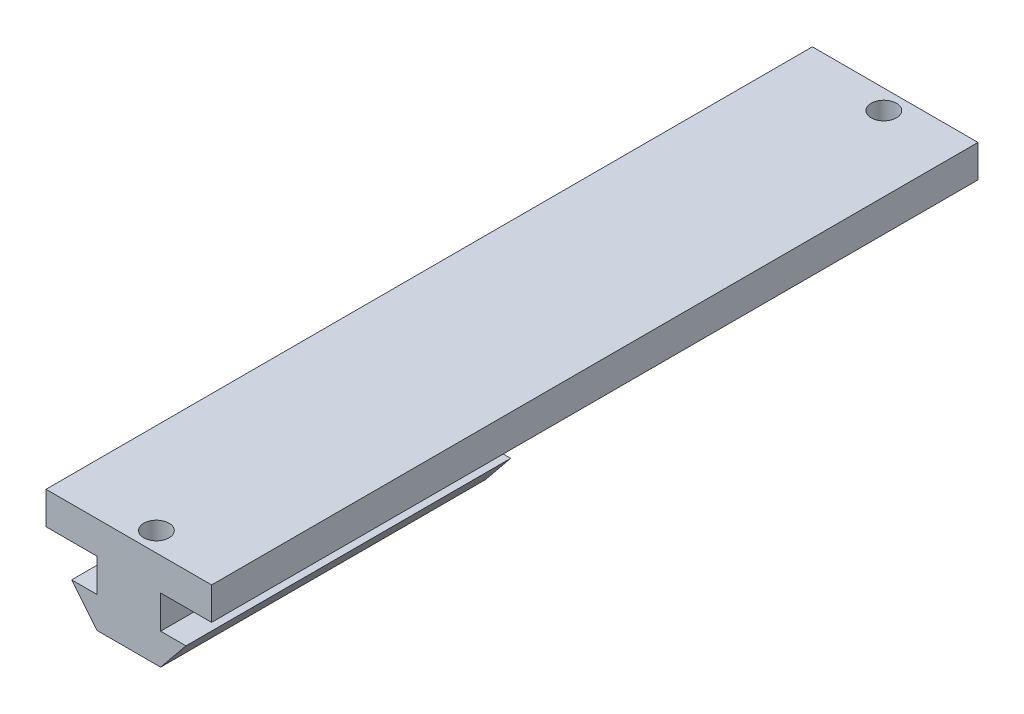
SolidWorks part; units mm, degrees
ref_plane "Front Plane" through (0, 0, 0) normal (0, 0, 1) x (1, 0, 0)
ref_plane "Top Plane" through (0, 0, 0) normal (0, 1, 0) x (1, 0, 0)
ref_plane "Right Plane" through (0, 0, 0) normal (1, 0, 0) x (0, 0, -1)
sketch "Sketch1" plane through (0, 0, 0) normal (0, 1, 0) x (1, 0, 0)
  line L1 (-12.75, -59) -> (12.75, -59)
  line L2 (-12.75, -59) -> (-12.75, 59)
  line L3 (-12.75, 59) -> (12.75, 59)
  line L4 (12.75, -59) -> (12.75, 59)
  line L5 (-12.75, -59) -> (12.75, 59) construction
  line L6 (-12.75, 59) -> (12.75, -59) construction
  point P0 (0, 0)
  dimension "D1" = 118
  dimension "D2" = 25.5
extrude "Boss-Extrude1" add sketch "Sketch1" along normal blind 5
sketch "Sketch2" plane through (0, 5, 0) normal (0, 1, 0) x (1, 0, 0)
  line L0 (12.75, 0) -> (-12.75, 0) construction
  line L1 (12.75, -59) -> (12.75, 59) construction
  line L2 (-12.75, 59) -> (-12.75, -59) construction
  circle A0 centre (1.25, 56) radius 1.95
  circle A1 centre (1.25, -56) radius 1.95
  dimension "D1" = 3.9
  dimension "D2" = 112
  dimension "D3" = 14
sketch "Sketch5" plane through (0, 0, 59) normal (0, 0, 1) x (1, 0, 0)
  line L1 (-12.75, 0) -> (12.75, 0) construction
  line L2 (-4.9, 0) -> (-4.9, -5.1)
  line L4 (-4.9, -9.9) -> (4.9, -9.9)
  line L6 (4.9, -5.1) -> (4.9, 0)
  line L7 (4.9, 0) -> (-4.9, 0)
  line L8 (0, 0) -> (0, -9.9) construction
  line L9 (-4.9, -5.1) -> (-8.8, -5.1)
  line L10 (-8.8, -5.1) -> (-4.9, -9.9)
  line L11 (4.9, -5.1) -> (8.8, -5.1)
  line L12 (8.8, -5.1) -> (4.9, -9.9)
  dimension "D1" = 5.1
  dimension "D2" = 4.8
  dimension "D3" = 3.9
  dimension "D4" = 9.8
extrude "Boss-Extrude5" add sketch "Sketch5" along direction (0, 0, -1) on the side against the normal blind 50
extrude "Cut-Extrude1" cut sketch "Sketch2" against normal blind 10
